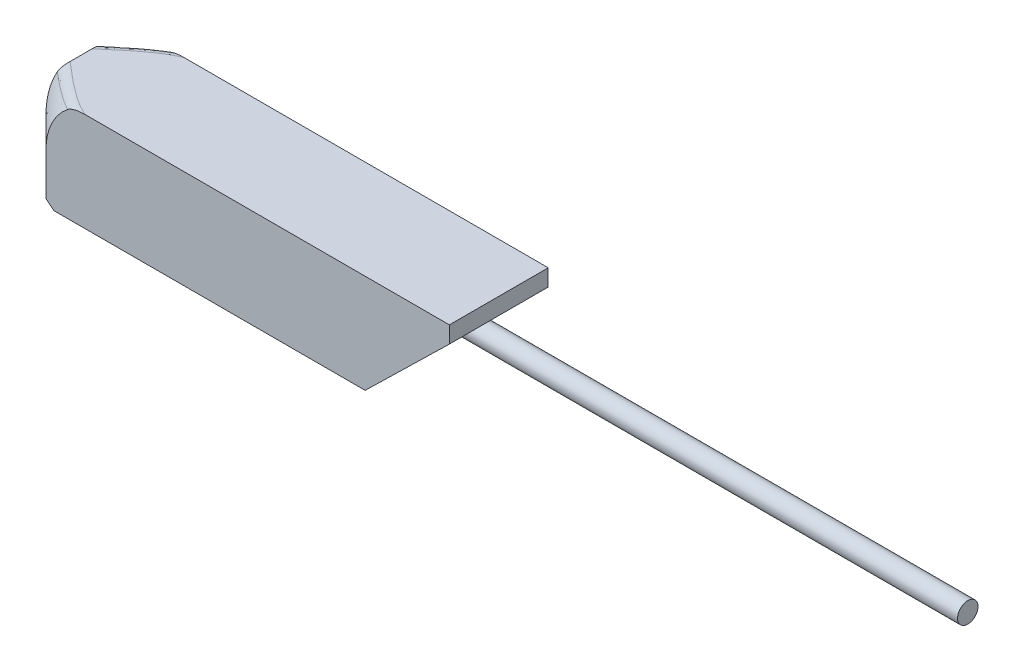
SolidWorks part; units mm, degrees
ref_plane "Front Plane" through (0, 0, 0) normal (0, 0, 1) x (1, 0, 0)
ref_plane "Top Plane" through (0, 0, 0) normal (0, 1, 0) x (1, 0, 0)
ref_plane "Right Plane" through (0, 0, 0) normal (1, 0, 0) x (0, 0, -1)
sketch "Sketch1" plane through (0, 0, 0) normal (0, 0, 1) x (1, 0, 0)
  line L0 (-200, 0) -> (200, 0)
  line L1 (-200, 0) -> (-200, -100)
  line L2 (-200, -100) -> (200, -100)
  line L3 (200, -100) -> (200, 0)
  dimension "D1" = 400
  dimension "D2" = 100
extrude "Boss-Extrude1" add sketch "Sketch1" along normal blind 100 contours L3 L0 L1 L2
sketch "Sketch2" plane through (0, 0, 100) normal (0, 0, 1) x (1, 0, 0)
  line L0 (-149.6112, 0) -> (-149.6112, -100) construction
  line L1 (-200, 0) -> (200, 0) construction
  line L2 (-200, -100) -> (200, -100) construction
  line L3 (-222.5805, 0) -> (-200, 0)
  line L4 (-200, 0) -> (-200, -100) construction
  line L5 (-200, 0) -> (-200, -50)
  line L6 (-200, -50) -> (-238.0675, -50)
  arc A0 (-222.5805, 0) -> (-238.0675, -50) centre (-149.6112, -50) ccw
extrude "Boss-Extrude2" add sketch "Sketch2" against normal blind 100 contours L6 A0 L3 L5
sketch "Sketch3" plane through (0, 0, 100) normal (0, 0, 1) x (1, 0, 0)
  line L0 (-238.0675, -50) -> (-238.0675, -69.8068)
  line L1 (-238.0675, -69.8068) -> (-200, -100)
  line L2 (-200, -100) -> (-200, -50)
  line L3 (-200, -50) -> (-238.0675, -50)
extrude "Boss-Extrude3" add sketch "Sketch3" against normal blind 100 contours L3 L0 L1 L2
chamfer "Chamfer1" distance 30 angle 45 2 edges at (-234.1071, -23.8282, 100) (-238.0675, -59.9034, 100)
chamfer "Chamfer2" distance 30 angle 45 2 edges at (-234.1071, -23.8282, 0) (-238.0675, -59.9034, 0)
fillet "Fillet1" radius 10 1 edges
fillet "Fillet2" radius 10 1 edges
sketch "Sketch4" plane through (-238.0675, 0, 0) normal (-1, 0, 0) x (0, 0, 1)
  line L0 (30, -59.9034) -> (30, -39.6909)
  line L1 (30, -50) -> (30, -69.8068) construction
  line L2 (30, -6.5246) -> (30, -50) construction
  line L3 (30, -39.6909) -> (70, -39.6909)
  line L4 (70, -50) -> (70, -6.5246) construction
  line L5 (70, -39.6909) -> (70, -59.9034)
  line L6 (70, -69.8068) -> (70, -50) construction
  line L7 (70, -59.9034) -> (30, -59.9034)
extrude "Cut-Extrude1" cut sketch "Sketch4" against normal blind 30 contours L7 L0 L3 L5
sketch "Sketch6" plane through (0, 0, 100) normal (0, 0, 1) x (1, 0, 0)
  line L0 (200, -16.8718) -> (114.7996, -100)
  line L1 (200, -100) -> (200, 0) construction
  line L2 (-200, -100) -> (200, -100) construction
  line L3 (114.7996, -100) -> (200, -100)
  line L4 (200, -100) -> (200, -16.8718)
extrude "Cut-Extrude2" cut sketch "Sketch6" against normal blind 240 contours L4 L0 L3
sketch "Sketch7" plane through (200, 0, 0) normal (1, 0, 0) x (0, 0, -1)
  line L0 (-95.9732, -16.8718) -> (-95.9732, -93.4681)
  line L1 (0, -16.8718) -> (-100, -16.8718) construction
  line L2 (-95.9732, -93.4681) -> (-6.7228, -93.4681)
  line L3 (-6.7228, -93.4681) -> (-6.7228, -16.8718)
  line L4 (-6.7228, -16.8718) -> (-95.9732, -16.8718)
extrude "Cut-Extrude3" cut sketch "Sketch7" against normal blind 80
sketch "Sketch8" plane through (120, 0, 0) normal (1, 0, 0) x (0, 0, -1)
  line L0 (-30, -39.6909) -> (-70, -39.6909) construction
  circle A0 centre (-50, -39.6909) radius 10.3458
extrude "Boss-Extrude5" add sketch "Sketch8" along normal blind 554.4201
sketch "Sketch9" plane through (0, 0, 100) normal (0, 0, 1) x (1, 0, 0)
  line L0 (-200, -100) -> (200, -100) construction
  line L1 (200, -100) -> (200, 0) construction
